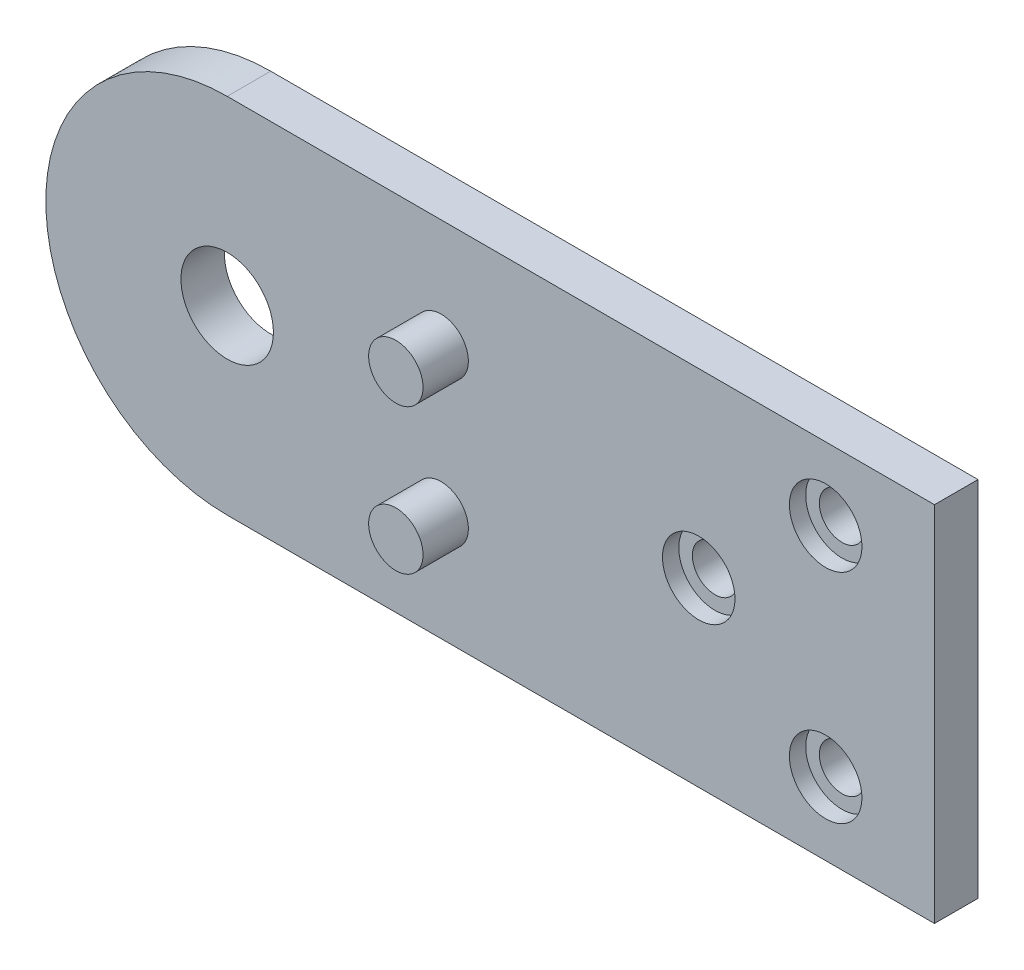
SolidWorks part; units mm, degrees
ref_plane "前视基准面" through (0, 0, 0) normal (0, 0, 1) x (1, 0, 0)
ref_plane "上视基准面" through (0, 0, 0) normal (0, 1, 0) x (1, 0, 0)
ref_plane "右视基准面" through (0, 0, 0) normal (1, 0, 0) x (0, 0, -1)
other "Configuration Table"
sketch "草图1" plane through (0, 0, 0) normal (0, 0, 1) x (1, 0, 0)
  line L5 (0, 10) -> (39, 10)
  line L6 (0, 10) -> (0, -10)
  line L7 (0, -10) -> (39, -10)
  line L8 (39, 10) -> (39, -10)
  circle A2 centre (0, 0) radius 10
  circle A9 centre (0, 0) radius 2.55
  circle A10 centre (0, 0) radius 1.1
  dimension "D1" = 20
  dimension "D2" = 39
extrude "凸台-拉伸1" add sketch "草图1" along normal blind 2.4 contours A2 | L7 L8 L5 L6
sketch "草图2" plane through (0, 0, 0) normal (0, 0, -1) x (-1, 0, 0)
  line L0 (0, 10) -> (-39, 10) construction
  line L1 (0, -10) -> (-39, -10) construction
  line L3 (-33, 6) -> (-33, -6) construction
  circle A0 centre (-33, 6) radius 2
  circle A1 centre (-33, 6) radius 1.25
  circle A2 centre (-33, -6) radius 2
  circle A3 centre (-33, -6) radius 1.25
  circle A4 centre (-26, 0) radius 2
  circle A5 centre (-26, 0) radius 1.25
  point P13 (-33, 0)
  dimension "D2" = 2.5
  dimension "D3" = 4
  dimension "D1" = 33
  dimension "D4" = 4
  dimension "D5" = 4
  dimension "D6" = 7
extrude "切除-拉伸1" cut sketch "草图2" against normal through all contours A1 | A3 | A5
extrude "切除-拉伸2" cut sketch "草图2<3>" along normal offset from surface (0.9 mm away) 1.5 from surface up to face at (31.75, 6, 0) starting at face at (31.75, 6, 2.4)
sketch "草图2<3>" plane through (0, 0, 0) normal (0, 0, -1) x (-1, 0, 0) same geometry as "草图2"
sketch "草图3" plane through (0, 0, 2.4) normal (0, 0, 1) x (1, 0, 0)
  circle A0 centre (0, 0) radius 2.55
  arc A1 (0, 10) -> (0, -10) centre (0, 0) ccw construction
  dimension "D1" = 5.1
extrude "切除-拉伸3" cut sketch "草图3" against normal through all
sketch "草图4" plane through (0, 0, 2.4) normal (0, 0, 1) x (1, 0, 0)
  line L0 (11.8, -4) -> (11.8, 4) construction
  line L1 (0, 0) -> (11.8, 0) construction
  circle A0 centre (11.8, -4) radius 1.5
  circle A1 centre (11.8, 4) radius 1.5
  dimension "D2" = 3
  dimension "D1" = 11.8
  dimension "D3" = 8
extrude "凸台-拉伸2" add sketch "草图4" along normal blind 2.5
